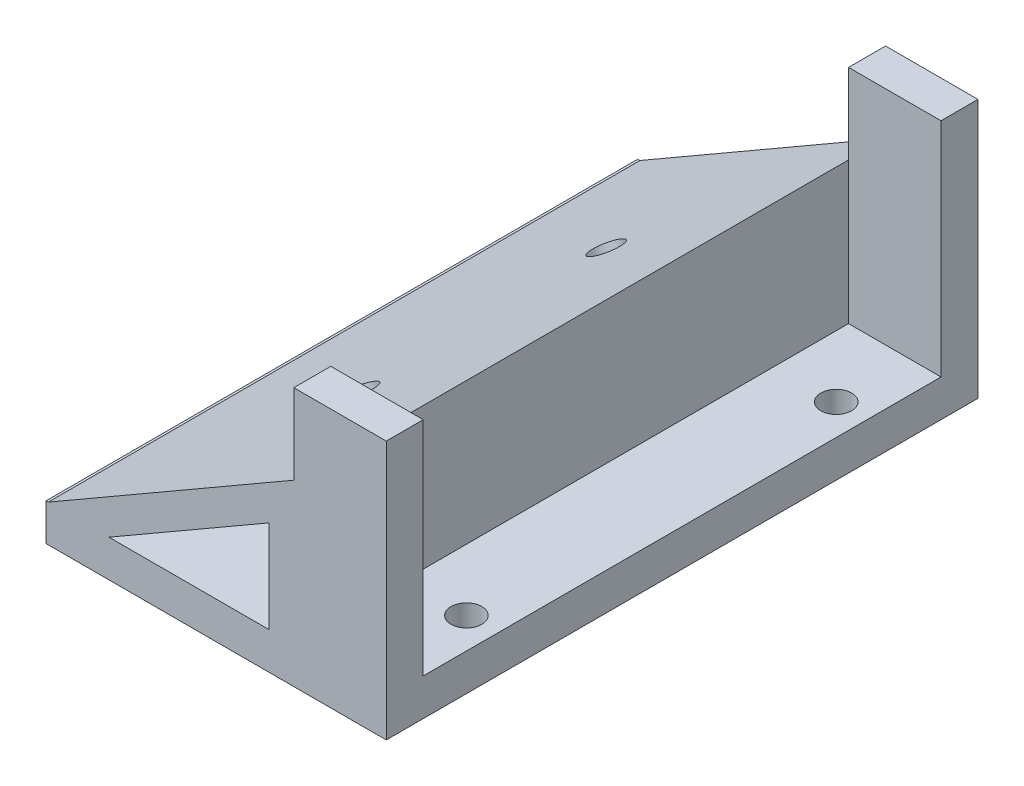
SolidWorks part; units mm, degrees
ref_plane "Front Plane" through (0, 0, 0) normal (0, 0, 1) x (1, 0, 0)
ref_plane "Top Plane" through (0, 0, 0) normal (0, 1, 0) x (1, 0, 0)
ref_plane "Right Plane" through (0, 0, 0) normal (1, 0, 0) x (0, 0, -1)
sketch "Sketch1" plane through (0, 0, 0) normal (0, 1, 0) x (1, 0, 0)
  line L1 (-70.1234, 25.0109) -> (-97.7234, 25.0109)
  line L2 (-70.1234, 25.0109) -> (-70.1234, 73.0109)
  line L3 (-70.1234, 73.0109) -> (-97.7234, 73.0109)
  line L4 (-97.7234, 25.0109) -> (-97.7234, 73.0109)
  dimension "D1" = 48
  dimension "D2" = 27.6
extrude "Boss-Extrude1" add sketch "Sketch1" along normal blind 3
sketch "Sketch2" plane through (0, 3, 0) normal (0, 1, 0) x (1, 0, 0)
  line L0 (-70.1234, 73.0109) -> (-97.7234, 73.0109) construction
  line L1 (-70.1234, 25.0109) -> (-70.1234, 73.0109) construction
  line L2 (-97.7234, 25.0109) -> (-70.1234, 25.0109) construction
  circle A1 centre (-82.6234, 65.264) radius 1.5
  circle A2 centre (-82.6234, 32.764) radius 1.5
  circle A3 centre (-72.6234, 34.0109) radius 1.25
  circle A4 centre (-72.6234, 64.0109) radius 1.25
  dimension "D8" = 3
  dimension "D9" = 3
  dimension "D10" = 2.5
  dimension "D11" = 2.5
  dimension "D1" = 30
  dimension "D2" = 32.5
  dimension "D3" = 10
  dimension "D4" = 10
  dimension "D5" = 9
  dimension "D6" = 2.5
  dimension "D7" = 2.5
  dimension "D12" = 7.7531
extrude "Cut-Extrude1" cut sketch "Sketch2" against normal through all
sketch "Sketch4" plane through (0, 0, -25.0109) normal (0, 0, 1) x (1, 0, 0)
  line L0 (-77.6234, 3) -> (-97.542, 3)
  line L2 (-97.542, 3) -> (-77.6234, 14.5)
  line L3 (-77.6234, 14.5) -> (-77.6234, 3)
  line L7 (-97.7234, 3) -> (-70.1234, 3) construction
  line L8 (-70.1234, 3) -> (-70.1234, 0) construction
  dimension "D1" = 23
  dimension "D2" = 30
  dimension "D3" = 60
  dimension "D4" = 7.5
extrude "Boss-Extrude2" add sketch "Sketch4" against normal blind 48 contours L0 L2 L3
sketch "Sketch6" plane through (0, 0, -25.0109) normal (0, 0, 1) x (1, 0, 0)
  line L0 (-92.6138, 3) -> (-79.6234, 3)
  line L2 (-92.6138, 3) -> (-79.6234, 10.5)
  line L3 (-79.6234, 10.5) -> (-79.6234, 3)
  line L10 (-77.6234, 3) -> (-70.1234, 3) construction
  dimension "D1" = 30
  dimension "D2" = 60
  dimension "D3" = 2
  dimension "D4" = 15
extrude "Cut-Extrude5" cut sketch "Sketch6" against normal through all contours L0 L3 L2
sketch "Sketch8" plane through (0, 3, 0) normal (0, 1, 0) x (1, 0, 0)
  circle A0 centre (-82.6234, 32.764) radius 2.5
  circle A1 centre (-82.6234, 32.764) radius 1.5 construction
  circle A2 centre (-82.6234, 65.264) radius 2.5
  circle A3 centre (-82.6234, 65.264) radius 1.5 construction
  dimension "D1" = 5
  dimension "D2" = 5
extrude "Cut-Extrude6" cut sketch "Sketch8" against normal blind 1
sketch "Sketch9" plane through (-25.6845, 44.4869, 0) normal (-0.5, 0.866, 0) x (0.866, 0.5, 0)
  line L0 (-82.9739, 73.0109) -> (-59.9739, 73.0109) construction
  line L1 (-59.9739, 73.0109) -> (-59.9739, 25.0109) construction
  circle A0 centre (-69.9739, 59.0109) radius 1.25
  circle A1 centre (-69.9739, 39.0109) radius 1.25
  dimension "D1" = 2.5
  dimension "D2" = 2.5
  dimension "D3" = 20
  dimension "D4" = 14
  dimension "D5" = 10
  dimension "D6" = 10
extrude "Cut-Extrude7" cut sketch "Sketch9" against normal up to next
sketch "Sketch10" plane through (-24.4525, 42.353, 0) normal (0.5, -0.866, 0) x (-0.866, -0.5, 0)
  circle A0 centre (69.9739, 59.0109) radius 2.5
  circle A1 centre (69.9739, 39.0109) radius 2.5
  circle A3 centre (69.9739, 39.0109) radius 1.25 construction
  circle A4 centre (69.9739, 59.0109) radius 1.25 construction
  dimension "D1" = 5
  dimension "D2" = 5
extrude "Cut-Extrude8" cut sketch "Sketch10" against normal blind 0.5
sketch "Sketch11" plane through (0, 3, 0) normal (0, 1, 0) x (1, 0, 0)
  line L0 (-77.6234, 25.0109) -> (-70.1234, 25.0109) construction
  line L1 (-70.1234, 25.0109) -> (-77.6234, 25.0109)
  line L2 (-70.1234, 25.0109) -> (-70.1234, 28.0109)
  line L3 (-70.1234, 28.0109) -> (-77.6234, 28.0109)
  line L4 (-77.6234, 25.0109) -> (-77.6234, 28.0109)
  line L5 (-70.1234, 70.0109) -> (-77.6234, 70.0109)
  line L6 (-70.1234, 70.0109) -> (-70.1234, 73.0109)
  line L7 (-70.1234, 73.0109) -> (-77.6234, 73.0109)
  line L8 (-77.6234, 70.0109) -> (-77.6234, 73.0109)
  line L9 (-70.1234, 73.0109) -> (-77.6234, 73.0109) construction
  line L10 (-70.1234, 25.0109) -> (-70.1234, 73.0109) construction
  line L11 (-77.6234, 73.0109) -> (-77.6234, 25.0109) construction
  dimension "D1" = 3
  dimension "D2" = 3
  dimension "D3" = 0
  dimension "D4" = 0
  dimension "D5" = 0
  dimension "D6" = 0
  dimension "D7" = 0
  dimension "D8" = 0
extrude "Boss-Extrude3" add sketch "Sketch11" along normal blind 18
